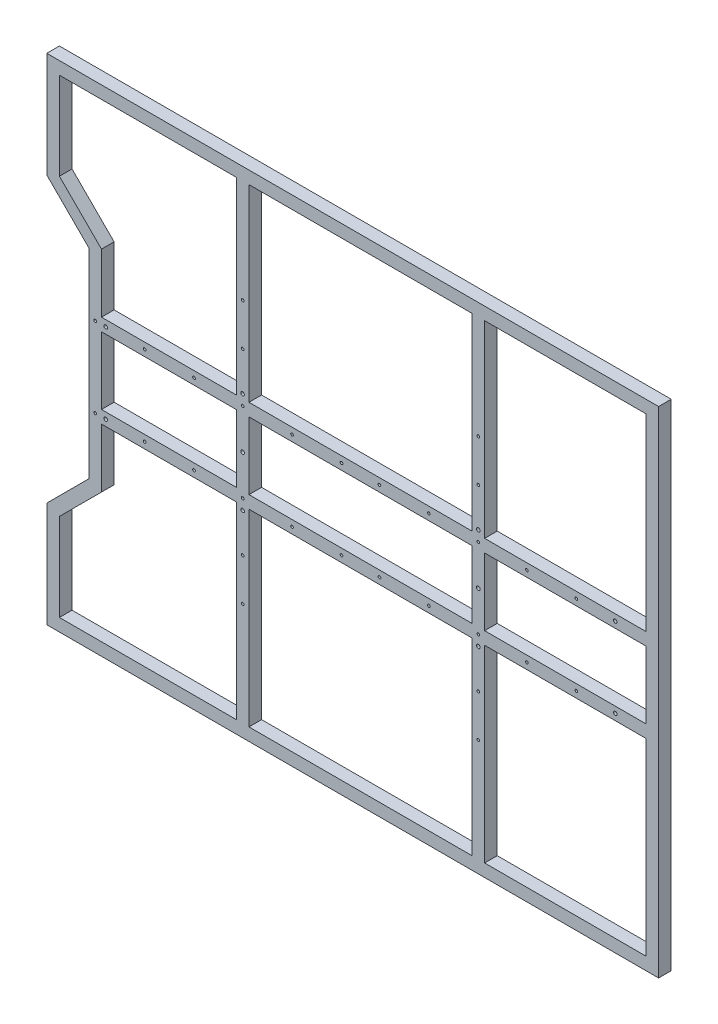
SolidWorks part; units mm, degrees
material "6061 合金"
ref_plane "前视基准面" through (0, 0, 0) normal (0, 0, 1) x (1, 0, 0)
ref_plane "上视基准面" through (0, 0, 0) normal (0, 1, 0) x (1, 0, 0)
ref_plane "右视基准面" through (0, 0, 0) normal (1, 0, 0) x (0, 0, -1)
sketch "草图2" plane through (0, 0, 0) normal (0, 0, 1) x (1, 0, 0)
  line L0 (0, 0) -> (56.6289, 0) construction
  line L1 (-372.7002, 294) -> (354.2002, 294)
  line L2 (-372.7002, 294) -> (-372.7002, 295.2267)
  line L3 (-357.7002, 279) -> (-147.5, 279)
  line L4 (354.2002, 294) -> (354.2002, 295)
  line L5 (-372.7002, 294) -> (-362.7002, 294)
  line L6 (-372.7002, 294) -> (-372.7002, 168.7868)
  line L8 (-357.7002, 279) -> (-357.7002, 175)
  line L10 (-372.7002, 168.7868) -> (-372.7002, 184.8427)
  line L17 (-307.7002, 40) -> (-147.5, 40)
  line L18 (-322.7002, 40.0093) -> (-322.7002, 55)
  line L19 (-307.7002, 55) -> (-147.5, 55)
  line L20 (354.2002, 40) -> (354.2002, 55)
  line L22 (354.2002, 40) -> (354.2002, 294)
  line L23 (354.2002, 294) -> (346.2002, 294)
  line L24 (339.2002, 55) -> (339.2002, 279)
  line L26 (147.5, 55) -> (147.5, 279)
  line L27 (147.5, 294) -> (132.5, 294)
  line L28 (132.5, 55) -> (132.5, 279)
  line L30 (-132.5, 55) -> (-132.5, 279)
  line L31 (-132.5, 294) -> (-147.5, 294)
  line L32 (-147.5, 55) -> (-147.5, 279)
  line L33 (291.2002, 87.1745) -> (291.2002, 179.4578) construction
  line L34 (-357.7002, 175) -> (-307.7002, 125)
  line L35 (-307.7002, 125) -> (-307.7002, 105)
  line L36 (-322.7002, 118.7868) -> (-372.7002, 168.7868)
  line L37 (-132.5, 55) -> (132.5, 55)
  line L38 (-322.7002, 118.7868) -> (-322.7002, 40.0093)
  line L39 (-307.7002, 125) -> (-307.7002, 55)
  line L40 (-132.5, 279) -> (132.5, 279)
  line L41 (147.5, 279) -> (339.2002, 279)
  line L42 (147.5, 55) -> (339.2002, 55)
  line L43 (147.5, -55) -> (339.2002, -55)
  line L44 (147.5, -279) -> (339.2002, -279)
  line L45 (-132.5, -279) -> (132.5, -279)
  line L46 (-307.7002, -125) -> (-307.7002, -55)
  line L47 (-322.7002, -118.7868) -> (-322.7002, -40.0093)
  line L48 (-132.5, -55) -> (132.5, -55)
  line L49 (-322.7002, -118.7868) -> (-372.7002, -168.7868)
  line L50 (-307.7002, -125) -> (-307.7002, -105)
  line L51 (-357.7002, -175) -> (-307.7002, -125)
  line L52 (-147.5, -55) -> (-147.5, -279)
  line L53 (-132.5, -294) -> (-147.5, -294)
  line L54 (-132.5, -55) -> (-132.5, -279)
  line L56 (132.5, -55) -> (132.5, -279)
  line L57 (147.5, -294) -> (132.5, -294)
  line L58 (147.5, -55) -> (147.5, -279)
  line L59 (-132.5, -40) -> (132.5, -40)
  line L60 (339.2002, -55) -> (339.2002, -279)
  line L61 (354.2002, -294) -> (346.2002, -294)
  line L62 (354.2002, -40) -> (354.2002, -294)
  line L63 (147.5, 40) -> (339.2002, 40)
  line L64 (354.2002, -40) -> (354.2002, -55)
  line L65 (-307.7002, -55) -> (-147.5, -55)
  line L66 (-322.7002, -40.0093) -> (-322.7002, -55)
  line L67 (-307.7002, -40) -> (-147.5, -40)
  line L68 (-372.7002, -168.7868) -> (-372.7002, -184.8427)
  line L69 (-366.6895, -163.0534) -> (-363.8898, -163.0534)
  line L70 (-357.7002, -279) -> (-357.7002, -175)
  line L71 (-366.6895, -163.0534) -> (-363.8898, -163.0534)
  line L72 (-372.7002, -294) -> (-372.7002, -168.7868)
  line L73 (-372.7002, -294) -> (-362.7002, -294)
  line L74 (354.2002, -294) -> (354.2002, -295)
  line L75 (-357.7002, -279) -> (-147.5, -279)
  line L76 (-372.7002, -294) -> (-372.7002, -295.2267)
  line L77 (-372.7002, -294) -> (354.2002, -294)
  line L78 (147.5, -40) -> (339.2002, -40)
  line L80 (-322.7002, 40.0093) -> (-322.7002, -40.0093)
  line L82 (-307.7002, 40) -> (-307.7002, -40)
  line L84 (-147.5, 40) -> (-147.5, -40)
  line L86 (-132.5, 40) -> (-132.5, -40)
  line L88 (132.5, 40) -> (132.5, -40)
  line L90 (147.5, 40) -> (147.5, -40)
  line L92 (339.2002, 40) -> (339.2002, -40)
  line L94 (354.2002, 40) -> (354.2002, -40)
  line L95 (-132.5, 40) -> (132.5, 40)
  circle A0 centre (140, 60) radius 2.1 construction
  circle A1 centre (-140, 60) radius 2.1 construction
  circle A2 centre (-302.7002, 47.5) radius 2.15 construction
  circle A3 centre (-327.7002, 47.5) radius 2.15 construction
  dimension "D8" = 7.5
  dimension "D9" = 7.5
  dimension "D11" = 7.5
  dimension "D12" = 15
  dimension "D15" = 5
  dimension "D1" = 15
  dimension "D2" = 15
  dimension "D3" = 15
  dimension "D4" = 15
  dimension "D5" = 50
  dimension "D6" = 15
  dimension "D7" = 15
  dimension "D10" = 224
  dimension "D13" = 15
  dimension "D14" = 48
  dimension "D16" = 15
  dimension "D17" = 50
  dimension "D18" = 70
  dimension "D19" = 135
extrude "凸台-拉伸1" add sketch "草图2" along normal blind 15 contours L94 L20 L22 L4 L1 L2 L6 L36 L38 L18 L80 L47 L49 L68 L72 L73 L77 L53 L57 L61 L62 L75 L70 L51 L46 L65 L52 L42 L26 region at (-367.7002, 284.6505, 0)
sketch "草图3" plane through (0, 0, 15) normal (0, 0, 1) x (1, 0, 0)
  line L0 (-170, 60) -> (-110, 60) construction
  line L1 (40.1698, 0) -> (-40.1698, 0) construction
  line L2 (0, 0) -> (0, 60) construction
  line L3 (-140, 153.0178) -> (-140, -19.3646) construction
  line L4 (-315.2002, 47.5) -> (315.2002, 47.5) construction
  line L5 (-307.7002, 55) -> (-147.5, 55) construction
  line L6 (-322.7002, 118.7868) -> (-322.7002, -118.7868) construction
  line L7 (140, 153.0178) -> (140, -19.3646) construction
  line L8 (170, 60) -> (110, 60) construction
  circle A0 centre (-140, 60) radius 2.15
  circle A1 centre (-315.2002, 47.5) radius 1.6
  circle A2 centre (-256.4668, 47.5) radius 1.6
  circle A3 centre (-197.7368, 47.5) radius 1.6
  circle A4 centre (-140, 47.5) radius 1.6
  circle A6 centre (-140, 156.23) radius 1.6
  circle A7 centre (-140, 106.23) radius 1.6
  circle A8 centre (-81.27, 47.5) radius 1.6
  circle A9 centre (-22.54, 47.5) radius 1.6
  circle A10 centre (-140, 0) radius 2.2407
  circle A11 centre (-302.7002, 47.5) radius 2.15 construction
  circle A12 centre (-302.7002, 47.5) radius 2.15
  circle A13 centre (-302.7002, -47.5) radius 2.15
  circle A14 centre (-22.54, -47.5) radius 1.6
  circle A15 centre (-81.27, -47.5) radius 1.6
  circle A16 centre (-140, -106.23) radius 1.6
  circle A17 centre (-140, -156.23) radius 1.6
  circle A18 centre (-140, -47.5) radius 1.6
  circle A19 centre (-197.7368, -47.5) radius 1.6
  circle A20 centre (-256.4668, -47.5) radius 1.6
  circle A21 centre (-315.2002, -47.5) radius 1.6
  circle A22 centre (-140, -60) radius 2.15
  circle A23 centre (140, -60) radius 2.15
  circle A25 centre (256.4668, -47.5) radius 1.6
  circle A26 centre (197.7368, -47.5) radius 1.6
  circle A27 centre (140, -47.5) radius 1.6
  circle A28 centre (140, -156.23) radius 1.6
  circle A29 centre (140, -106.23) radius 1.6
  circle A30 centre (81.27, -47.5) radius 1.6
  circle A31 centre (22.54, -47.5) radius 1.6
  circle A32 centre (302.7002, -47.5) radius 2.15
  circle A33 centre (302.7002, 47.5) radius 2.15
  circle A34 centre (140, 0) radius 2.2407
  circle A35 centre (22.54, 47.5) radius 1.6
  circle A36 centre (81.27, 47.5) radius 1.6
  circle A37 centre (140, 106.23) radius 1.6
  circle A38 centre (140, 156.23) radius 1.6
  circle A39 centre (140, 47.5) radius 1.6
  circle A40 centre (197.7368, 47.5) radius 1.6
  circle A41 centre (256.4668, 47.5) radius 1.6
  circle A43 centre (140, 60) radius 2.15
  point P63 (0, 47.5)
  dimension "D1" = 4.3
  dimension "D10" = 3.2
  dimension "D2" = 7.5
  dimension "D3" = 7.5
  dimension "D4" = 58.7333
  dimension "D5" = 58.73
  dimension "D6" = 58.73
  dimension "D7" = 50
  dimension "D8" = 58.73
  dimension "D9" = 58.73
extrude "切除-拉伸1" cut sketch "草图3" against normal blind 15
